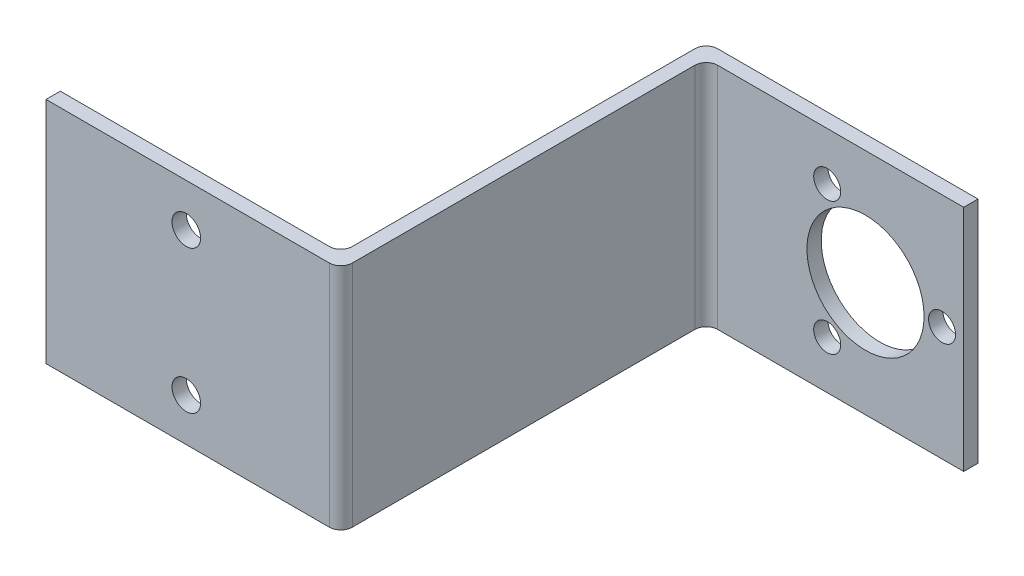
SolidWorks part; units mm, degrees
material "AISI 1020 Steel, Cold Rolled"
ref_plane "Front Plane" through (0, 0, 0) normal (0, 0, 1) x (1, 0, 0)
ref_plane "Top Plane" through (0, 0, 0) normal (0, 1, 0) x (1, 0, 0)
ref_plane "Right Plane" through (0, 0, 0) normal (1, 0, 0) x (0, 0, -1)
sketch "Sketch2" plane through (0, 0, 0) normal (0, 1, 0) x (1, 0, 0)
  line L0 (-882.1327, -41.9257) -> (-912.2952, -41.9257)
  line L1 (-912.2952, -41.9257) -> (-912.2952, -82.4882)
  line L2 (-912.2952, -82.4882) -> (-943.4327, -82.4882)
  line L3 (-943.4327, -82.4882) -> (-943.4327, -84.0757)
  line L4 (-943.4327, -84.0757) -> (-910.7077, -84.0757)
  line L5 (-910.7077, -84.0757) -> (-910.7077, -43.5132)
  line L6 (-910.7077, -43.5132) -> (-882.1327, -43.5132)
  line L7 (-882.1327, -43.5132) -> (-882.1327, -41.9257)
  line L8 (-912.2952, -62.207) -> (-910.7077, -62.207) construction
  line L9 (-926.2764, -84.0757) -> (-929.4514, -84.0757) construction
  line L10 (-918.0327, -109.4757) -> (-918.0327, -84.0757) construction
  dimension "D1" = 1.5875
  dimension "D2" = 25.4
  dimension "D3" = 3.175
extrude "Boss-Extrude2" add sketch "Sketch2" along normal blind 25.4
sketch "Sketch3" plane through (0, 0, 43.5132) normal (0, 0, 1) x (1, 0, 0)
  arc A0 (-896.5327, 18.7622) -> (-898.0327, 21.3603) centre (-897.2827, 20.0612) ccw construction
  arc A1 (-886.0327, 12.7) -> (-883.0327, 12.7) centre (-884.5327, 12.7) ccw construction
  arc A2 (-883.0327, 12.7) -> (-886.0327, 12.7) centre (-884.5327, 12.7) ccw construction
  arc A3 (-898.0327, 21.3603) -> (-896.5327, 18.7622) centre (-897.2827, 20.0612) ccw construction
  arc A4 (-886.0327, 12.7) -> (-883.0327, 12.7) centre (-884.5327, 12.7) ccw
  arc A5 (-883.0327, 12.7) -> (-886.0327, 12.7) centre (-884.5327, 12.7) ccw
  arc A6 (-896.5327, 18.7622) -> (-898.0327, 21.3603) centre (-897.2827, 20.0612) ccw
  arc A7 (-898.0327, 21.3603) -> (-896.5327, 18.7622) centre (-897.2827, 20.0612) ccw
  arc A8 (-898.0327, 4.0397) -> (-896.5327, 6.6378) centre (-897.2827, 5.3388) ccw construction
  arc A9 (-896.5327, 6.6378) -> (-898.0327, 4.0397) centre (-897.2827, 5.3388) ccw construction
  arc A10 (-898.0327, 4.0397) -> (-896.5327, 6.6378) centre (-897.2827, 5.3388) ccw
  arc A11 (-896.5327, 6.6378) -> (-898.0327, 4.0397) centre (-897.2827, 5.3388) ccw
  arc A12 (-899.5327, 12.7) -> (-886.5327, 12.7) centre (-893.0327, 12.7) ccw construction
  arc A13 (-886.5327, 12.7) -> (-899.5327, 12.7) centre (-893.0327, 12.7) ccw construction
  arc A14 (-899.5327, 12.7) -> (-886.5327, 12.7) centre (-893.0327, 12.7) ccw
  arc A15 (-886.5327, 12.7) -> (-899.5327, 12.7) centre (-893.0327, 12.7) ccw
extrude "Cut-Extrude1" cut sketch "Sketch3" against normal through all
hole_wizard "1/8 (0.125) Diameter Hole1" positions "Sketch7" profile "Sketch8" hole size "1/8" standard "ANSI Inch" end condition through all
sketch "Sketch7" plane through (0, 0, 82.4882) normal (0, 0, -1) x (-1, 0, 0)
  line L1 (927.8639, 25.4) -> (927.8639, 20.6375) construction
  line L2 (912.2952, 25.4) -> (943.4327, 25.4) construction
  line L3 (927.8639, 20.6375) -> (927.8639, 4.7625) construction
  line L4 (927.8639, 4.7625) -> (927.8639, 0) construction
  line L5 (912.2952, 0) -> (943.4327, 0) construction
  line L7 (918.0327, 25.4) -> (943.4327, 25.4)
  line L9 (918.0327, -19.05) -> (918.0327, 44.45) construction
  point P27 (927.8639, 20.6375)
  point P30 (927.8639, 4.7625)
  dimension "D1" = 4.7625
sketch "Sketch8" plane through (-927.8639, 4.7625, 82.4882) normal (1, 0, 0) x (0, 1, 0)
  line L0 (0, 0) -> (0, 1.5875)
  line L1 (0, 1.5875) -> (1.5875, 1.5875)
  line L2 (1.5875, 1.5875) -> (1.5875, 0)
  line L5 (1.5875, 0) -> (0, 0)
  line L11 (0, -6.35) -> (0, 107.95) construction
  dimension "Thru Hole Dia." = 3.175
  dimension "Thru Hole Depth" = 1.5875
fillet "Fillet1" radius 1.27 4 edges at (-912.2952, 12.7, 82.4882) (-910.7077, 12.7, 43.5132) (-912.2952, 12.7, 41.9257) (-910.7077, 12.7, 84.0757)
